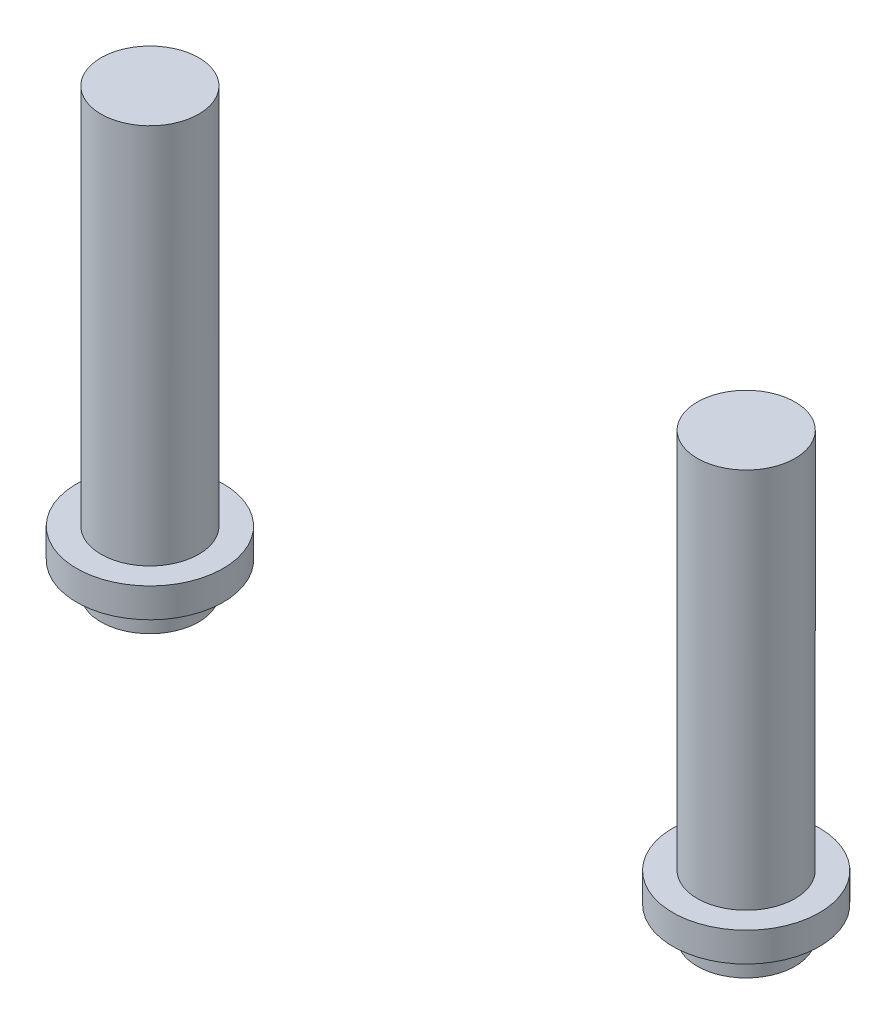
SolidWorks part; units mm, degrees
ref_plane "前视基准面" through (0, 0, 0) normal (0, 0, 1) x (1, 0, 0)
ref_plane "上视基准面" through (0, 0, 0) normal (0, 1, 0) x (1, 0, 0)
ref_plane "右视基准面" through (0, 0, 0) normal (1, 0, 0) x (0, 0, -1)
other "Configuration Table"
sketch "草图1" plane through (0, 0, 0) normal (0, 1, 0) x (1, 0, 0)
  line L0 (50, 0) -> (50, 85.1816) construction
  line L1 (0, 0) -> (100, 0)
  line L2 (0, 0) -> (0, -100)
  line L3 (0, -100) -> (100, -100)
  line L4 (100, 0) -> (100, -100)
  line L5 (9.5, 75.0478) -> (9.5, 17.1128) construction
  line L6 (90.5, 75.0478) -> (90.5, 17.1128) construction
  line L7 (-7.6482, 80) -> (134.4168, 80) construction
  line L8 (0, 0) -> (9.5, 12.5)
  line L9 (100, 0) -> (90.5, 12.5)
  line L10 (90.5, 12.5) -> (90.5, 212.5)
  line L11 (90.5, 212.5) -> (9.5, 212.5)
  line L12 (9.5, 212.5) -> (9.5, 12.5)
  line L13 (90.5, 12.5) -> (90.5, 0)
  line L14 (9.5, 12.5) -> (9.5, 0)
  dimension "D1" = 100
  dimension "D2" = 100
  dimension "D3" = 81
  dimension "D4" = 80
  dimension "D5" = 200
extrude "凸台-拉伸1" add sketch "草图1" along normal blind 50 and the other way blind 50 contours L12 L14 L1 L13 L10 L11 region at (50, 0, -106.25)
ref_plane "基准面1" through (0, 0, 0) normal (0, -1, 0) x (-1, 0, 0)
sketch "草图2" plane through (0, 0, 0) normal (0, -1, 0) x (-1, 0, 0)
  line L0 (-130.3132, 0) -> (40.2206, 0) construction
  line L1 (-150, 0) -> (-150, -100)
  line L2 (-150, -100) -> (50, -100)
  line L3 (50, -100) -> (50, 0)
  line L4 (50, 0) -> (-150, 0)
  line L5 (-50, 212.5) -> (-50, 195.989) construction
  line L6 (-90.5, 212.5) -> (-9.5, 212.5) construction
  point P10 (-50, 212.5)
  dimension "D1" = 200
  dimension "D2" = 100
extrude "凸台-拉伸2" add sketch "草图2" against normal blind 40
ref_plane "基准面2" through (0, 0, 100) normal (0, 0, 1) x (1, 0, 0)
sketch "草图3" plane through (0, 0, 100) normal (0, 0, 1) x (1, 0, 0)
  line L0 (-50, 37) -> (150, 37)
  line L1 (-50, 40) -> (-50, 0) construction
  line L2 (150, 40) -> (150, 0) construction
  line L3 (150, 37) -> (150, 3)
  line L4 (150, 3) -> (-50, 3)
  line L5 (-50, 3) -> (-50, 37)
  line L6 (150, 0) -> (-50, 0) construction
  line L7 (150, 40) -> (-50, 40) construction
  dimension "D1" = 3
  dimension "D2" = 3
extrude "切除-拉伸1" cut sketch "草图3" against normal blind 100
ref_plane "基准面3" through (34.5, 0, 0) normal (-1, 0, 0) x (0, 0, 1)
ref_plane "基准面4" through (0, 50, 0) normal (0, 1, 0) x (1, 0, 0)
sketch "草图6" plane through (0, 50, 0) normal (0, 1, 0) x (1, 0, 0)
  line L0 (12.5, 212.5) -> (12.5, 5)
  line L1 (90.5, 212.5) -> (9.5, 212.5) construction
  line L2 (12.5, 5) -> (87.5, 5)
  line L3 (87.5, 5) -> (87.5, 212.5)
  line L4 (9.5, 212.5) -> (9.5, 0) construction
  line L5 (90.5, 212.5) -> (90.5, 0) construction
  line L7 (9.5, 0) -> (90.5, 0) construction
  dimension "D1" = 3
  dimension "D2" = 3
  dimension "D3" = 5
extrude "切除-拉伸2" cut sketch "草图6" against normal through all
ref_plane "基准面5" through (0, 40, 0) normal (0, 1, 0) x (1, 0, 0)
sketch "草图8" plane through (0, 40, 0) normal (0, 1, 0) x (1, 0, 0)
  line L0 (-50, -50) -> (102.2011, -50) construction
  line L1 (-50, -100) -> (-50, 0) construction
  line L2 (50, 0) -> (50, -100) construction
  line L3 (9.5, 0) -> (90.5, 0) construction
  line L4 (-22, -100) -> (22, -100) construction
  circle A0 centre (70, -50) radius 2.5
  circle A1 centre (30, -50) radius 2.5
  dimension "D1" = 5
  dimension "D2" = 5
  dimension "D3" = 40
extrude "切除-拉伸4" cut sketch "草图8" against normal through all
ref_plane "基准面6" through (90.5, 0, 0) normal (1, 0, 0) x (0, 0, -1)
sketch "草图10" plane through (90.5, 0, 0) normal (1, 0, 0) x (0, 0, -1)
  line L0 (39.5916, 0) -> (155.7144, 0) construction
  line L2 (0, 37) -> (0, 3) construction
  circle A0 centre (80, 0) radius 5
  circle A1 centre (180, 0) radius 5
  dimension "D3" = 10
  dimension "D4" = 10
  dimension "D1" = 80
  dimension "D2" = 180
extrude "切除-拉伸5" cut sketch "草图10" against normal through all
sketch "草图11" plane through (9.5, 0, 0) normal (-1, 0, 0) x (0, 0, 1)
  line L2 (-30.9056, 83.4152) -> (-74.0944, 50)
  line L3 (44.55, 50) -> (-44.55, 50) construction
  line L4 (-74.0944, 50) -> (0, 50)
  line L5 (0, 40) -> (0, 50) construction
  line L6 (0, 50) -> (0, 40)
  line L8 (-30.9056, 83.4152) -> (83.321, 40)
  line L9 (100, 40) -> (0, 40) construction
  line L10 (83.321, 40) -> (0, 40)
extrude "凸台-拉伸5" add sketch "草图11" against normal blind 20
sketch "草图13" plane through (90.5, 0, 0) normal (1, 0, 0) x (0, 0, -1)
  line L0 (0, 36.2107) -> (0, 62.8442) construction
  line L1 (44.55, 50) -> (-44.55, 50) construction
  line L2 (74.1158, 50) -> (0, 50)
  line L3 (74.1158, 50) -> (74.1158, 53)
  line L4 (74.1158, 53) -> (0, 53)
  line L5 (0, 50) -> (0, 53)
  dimension "D1" = 3
extrude "凸台-拉伸7" add sketch "草图13" against normal blind 81
ref_plane "基准面7" through (12.5, 0, 0) normal (1, 0, 0) x (0, 0, -1)
sketch "草图14" plane through (12.5, 0, 0) normal (1, 0, 0) x (0, 0, -1)
  line L0 (5, -46.5508) -> (5, 34.4221) construction
  line L2 (5, -50) -> (212.5, -50)
  line L3 (212.5, -50) -> (212.5, 50)
  line L4 (44.55, 50) -> (-44.55, 50) construction
  line L5 (212.5, -50) -> (212.5, 50) construction
  line L6 (212.5, 50) -> (5, 50)
  line L7 (5, 50) -> (5, -50)
extrude "凸台-拉伸8" add sketch "草图14" along normal blind 7
sketch "草图15" plane through (90.5, 0, 0) normal (1, 0, 0) x (0, 0, -1)
  line L0 (30.9056, 83.4152) -> (-82.9022, 40)
  line L1 (55, 40) -> (-55, 40) construction
  line L2 (-82.9022, 40) -> (0, 40)
  line L3 (0, 37) -> (0, 40) construction
  line L4 (0, 40) -> (0, 53)
  line L5 (0, 53) -> (70.217, 53)
  line L6 (70.217, 53) -> (30.9056, 83.4152)
extrude "凸台-拉伸9" add sketch "草图15" against normal blind 20
ref_plane "基准面8" through (0, 37, 0) normal (0, -1, 0) x (-1, 0, 0)
ref_plane "基准面9" through (0, 3, 0) normal (0, 1, 0) x (1, 0, 0)
sketch "草图17" plane through (0, 37, 0) normal (0, -1, 0) x (-1, 0, 0)
  circle A0 centre (-30, -50) radius 6.35
  dimension "D1" = 12.7
extrude "切除-拉伸6" cut sketch "草图17" against normal blind 1
sketch "草图18" plane through (0, 3, 0) normal (0, 1, 0) x (1, 0, 0)
  circle A0 centre (30, -50) radius 6.35
  dimension "D1" = 12.7
extrude "切除-拉伸7" cut sketch "草图18" against normal blind 1
sketch "草图20" plane through (0, 0, 0) normal (0, -1, 0) x (1, 0, 0)
  line L0 (7.57, 50) -> (34.6356, 50) construction
  line L1 (30, 52.5) -> (30, 68.4286) construction
  circle A1 centre (-31.25, 50) radius 5
  circle A2 centre (91.25, 50) radius 5
  dimension "D2" = 10
  dimension "D4" = 10
  dimension "D1" = 61.25
  dimension "D3" = 61.25
extrude "切除-拉伸8" cut sketch "草图20" against normal blind 3
cosmetic thread "装饰螺纹线1" parameters "D2"=11
cosmetic thread "装饰螺纹线2" parameters "D2"=11
sketch "草图21" plane through (0, 3, 0) normal (0, 1, 0) x (1, 0, 0)
  line L0 (118.3346, -100) -> (118.3346, 0)
  line L1 (-1.65, -100) -> (1.65, -100) construction
  line L2 (90.5, 0) -> (150, 0) construction
  line L3 (118.3346, 0) -> (150, 0)
  line L4 (150, 0) -> (150, -100)
  line L5 (150, 0) -> (150, -100) construction
  line L6 (150, -100) -> (118.3346, -100)
extrude "切除-拉伸9" cut sketch "草图21" along normal through all both and the other way through all
sketch "草图22" plane through (0, 0, 0) normal (0, -1, 0) x (1, 0, 0)
  line L0 (-38.0419, 14.9384) -> (110.8032, 14.9384) construction
  circle A0 centre (-28.835, 14.9384) radius 5
  circle A1 centre (99.9437, 14.9384) radius 5
  circle A2 centre (47.3586, 88.9028) radius 5
  dimension "D1" = 10
  dimension "D2" = 10
  dimension "D3" = 10
extrude "凸台-拉伸10" add sketch "草图22" against normal up to surface (37 mm away) up to face at (70, 37, 52.5)
fillet "圆角1" radius 30 10 edges at (19.5, 83.4152, -30.9056) (80.5, 83.4152, -30.9056) (118.3346, 38.5, 0) (118.3346, 1.5, 0) (118.3346, 38.5, 100) (118.3346, 1.5, 100) (-50, 38.5, 100) (-50, 38.5, 0) (-50, 1.5, 0) (-50, 1.5, 100)
fillet "圆角2" radius 30 2 edges at (89, -50, -212.5) (89, 50, -212.5)
sketch "草图23" plane through (90.5, 0, 0) normal (1, 0, 0) x (0, 0, -1)
  line L0 (55, 40) -> (-55, 40) construction
  line L1 (0, 40) -> (-157.2114, 40)
  line L2 (0, 40) -> (0, -63.2192)
  line L3 (0, -63.2192) -> (-157.2114, -63.2192)
  line L4 (-157.2114, 40) -> (-157.2114, -63.2192)
extrude "切除-拉伸10" cut sketch "草图23" against normal through all both and the other way through all
sketch "草图24" plane through (0, 40, 0) normal (0, -1, 0) x (1, 0, 0)
  line L0 (80.5, 0) -> (80.5, 28.8779) construction
  line L1 (70.5, 0) -> (90.5, 0) construction
  line L2 (19.5, 0) -> (19.5, 26.1524) construction
  line L3 (9.5, 0) -> (29.5, 0) construction
  circle A0 centre (80.5, 10) radius 5
  circle A1 centre (19.5, 10) radius 5
  dimension "D1" = 10
  dimension "D3" = 10
  dimension "D2" = 10
extrude "凸台-拉伸11" add sketch "草图24" along normal blind 40
cosmetic thread "装饰螺纹线3" parameters "D1"=7, "D2"=9
cosmetic thread "装饰螺纹线4" parameters "D1"=7, "D2"=9
ref_plane "基准面10" through (0, 3, 0) normal (0, -1, 0) x (-1, 0, 0)
sketch "草图25" plane through (0, 3, 0) normal (0, -1, 0) x (-1, 0, 0)
  circle A0 centre (-80.5, -10) radius 7.5
  circle A1 centre (-19.5, -10) radius 7.5
  dimension "D1" = 15
  dimension "D2" = 15
extrude "凸台-拉伸12" add sketch "草图25" against normal blind 3
sketch "草图26" plane through (90.5, 0, 0) normal (1, 0, 0) x (0, 0, -1)
  line L0 (0, 40) -> (-95.7763, 40)
  line L1 (55, 40) -> (-55, 40) construction
  line L2 (-95.7763, 40) -> (-95.7763, 80.954)
  line L3 (-95.7763, 80.954) -> (216.9094, 89.1645)
  line L4 (216.9094, 89.1645) -> (220.7056, -55.4049)
  line L5 (220.7056, -55.4049) -> (-26.2146, -67.7485)
  line L6 (-26.2146, -67.7485) -> (0, -42.4326)
  line L7 (0, -50) -> (0, 40) construction
  line L8 (0, -42.4326) -> (0, 40)
extrude "切除-拉伸11" cut sketch "草图26" against normal through all both and the other way through all
sketch "草图27" plane through (0, 40, 0) normal (0, 1, 0) x (1, 0, 0)
  circle A0 centre (80.5, -10) radius 5
  circle A1 centre (19.5, -10) radius 5
extrude "凸台-拉伸13" add sketch "草图27" along normal blind 5
